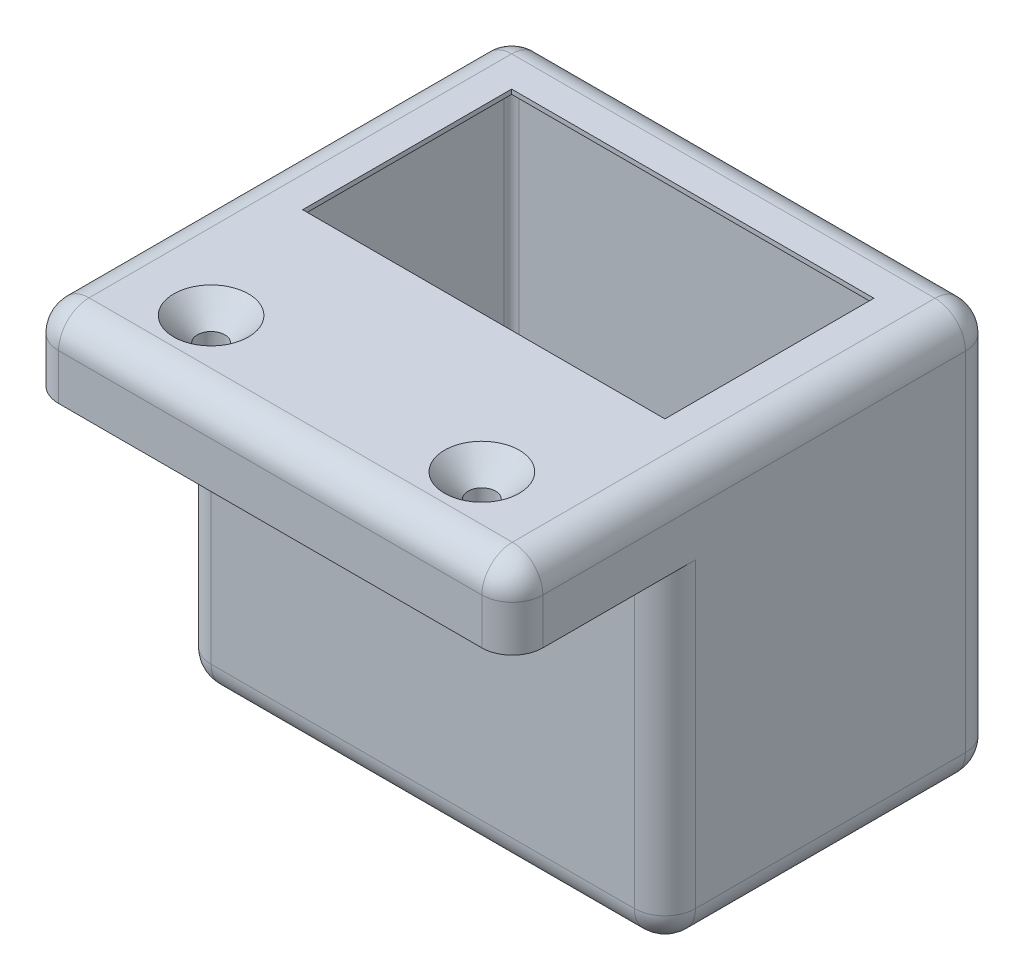
SolidWorks part; units mm, degrees
ref_plane "Front Plane" through (0, 0, 0) normal (0, 0, 1) x (1, 0, 0)
ref_plane "Top Plane" through (0, 0, 0) normal (0, 1, 0) x (1, 0, 0)
ref_plane "Right Plane" through (0, 0, 0) normal (1, 0, 0) x (0, 0, -1)
sketch "Profile Sketch" plane through (0, 0, 0) normal (1, 0, 0) x (0, 0, -1)
  line L0 (0, 0) -> (0, 43.6)
  line L1 (0, 43.6) -> (-20, 43.6)
  line L2 (-20, 43.6) -> (-20, 53.6)
  line L3 (-20, 53.6) -> (43.4, 53.6)
  line L4 (43.4, 53.6) -> (43.4, 0)
  line L5 (43.4, 0) -> (0, 0)
  dimension "D1" = 63.4
  dimension "D2" = 10
  dimension "D3" = 43.4
  dimension "D4" = 53.6
extrude "Profile Extrude" add sketch "Profile Sketch" along normal mid plane 63.5
sketch "Interior Sketch" plane through (0, 0, 0) normal (0, -1, 0) x (1, 0, 0)
  line L8 (-28.75, -3) -> (-28.75, -40.4)
  line L9 (-28.75, -40.4) -> (28.75, -40.4)
  line L10 (28.75, -40.4) -> (28.75, -3)
  line L11 (28.75, -3) -> (-28.75, -3)
  line L12 (-28.75, -3) -> (-28.75, -40.4)
  line L13 (-28.75, -40.4) -> (28.75, -40.4)
  line L14 (28.75, -40.4) -> (28.75, -3)
  line L15 (28.75, -3) -> (-28.75, -3)
  dimension "D1" = 3
extrude "Interior Cut" cut sketch "Interior Sketch" against normal offset from surface (50 mm away) 0.6 from offset 3 up to face at (0, 53.6, -11.7) offset against normal yes
sketch "Opening Sketch" plane through (0, 53.6, 0) normal (0, 1, 0) x (1, 0, 0)
  line L8 (-23.75, 8) -> (23.75, 8)
  line L9 (-23.75, 35.4) -> (-23.75, 8)
  line L10 (23.75, 35.4) -> (-23.75, 35.4)
  line L11 (23.75, 8) -> (23.75, 35.4)
  line L12 (-23.75, 8) -> (23.75, 8)
  line L13 (-23.75, 35.4) -> (-23.75, 8)
  line L14 (23.75, 35.4) -> (-23.75, 35.4)
  line L15 (23.75, 8) -> (23.75, 35.4)
  dimension "D1" = 5
extrude "Opening Cut" cut sketch "Opening Sketch" against normal up to next
chamfer "Chamfer1" distance 5 angle 45 4 edges at (28.75, 53, -21.7) (0, 53, -40.4) (-28.75, 53, -21.7) (0, 53, -3)
fillet "Fillet1" radius 1 4 edges at (-28.75, 25.5, -3) (28.75, 25.5, -3) (28.75, 25.5, -40.4) (-28.75, 25.5, -40.4)
sketch "Sketch5" plane through (0, 0, 0) normal (0, -1, 0) x (1, 0, 0)
  line L0 (-31.75, -43.4) -> (31.75, 0) construction
  circle A0 centre (0, -21.7) radius 9.5
  dimension "D1" = 19
extrude "Cut-Extrude3" cut sketch "Sketch5" against normal up to next
fillet "Fillet2" 2 edges at (0, 0, -31.2) (0, 3, -31.2) type full round first side face at (0, 0, -31.2) second side face at (0, 3, -31.2) middle face at (0, 0, -31.2)
fillet "Fillet3" radius 4 14 edges at (0, 0, 0) (31.75, 0, -21.7) (0, 0, -43.4) (-31.75, 0, -21.7) (-31.75, 26.8, -43.4) (0, 53.6, -43.4) (31.75, 26.8, -43.4) (-31.75, 21.8, 0) (31.75, 21.8, 0) (-31.75, 53.6, -11.7) (-31.75, 48.6, 20) (0, 53.6, 20) (31.75, 53.6, -11.7) (31.75, 48.6, 20)
sketch "Mounting Hole Layout Sketch" plane through (0, 53.6, 0) normal (0, 1, 0) x (1, 0, 0)
  line L0 (0, 0) -> (0, -27.8287) construction
  line L1 (27.75, -20) -> (-27.75, -20) construction
  point P3 (-17.75, -10)
  point P4 (17.75, -10)
  dimension "D1" = 35.5
  dimension "D2" = 10
hole_wizard "CSK for M3 Flat Head Machine Screw1" positions "3DSketch1" profile "Sketch7" countersink size "M3" standard "ANSI Metric" end condition up to next
sketch3d "3DSketch1"
  point P0 (-17.75, 53.6, 10)
  point P3 (17.75, 53.6, 10)
sketch "Sketch7" plane through (-17.75, 53.6, 10) normal (1, 0, 0) x (0, 0, 1)
  line L0 (0, 0) -> (0, 10)
  line L1 (0, 10) -> (1.8, 10)
  line L2 (1.8, 10) -> (1.8, 3.1)
  line L3 (1.8, 3.1) -> (4.9, 0)
  line L5 (4.9, 0) -> (0, 0)
  line L6 (-1.8, 3.1) -> (-4.9, 0) construction
  line L11 (0, -6.35) -> (0, 107.95) construction
  dimension "Thru Hole Dia." = 3.6
  dimension "Thru Hole Depth" = 10
  dimension "Near C'Sink Dia." = 9.8
  dimension "Near C'Sink Angle" = 90
